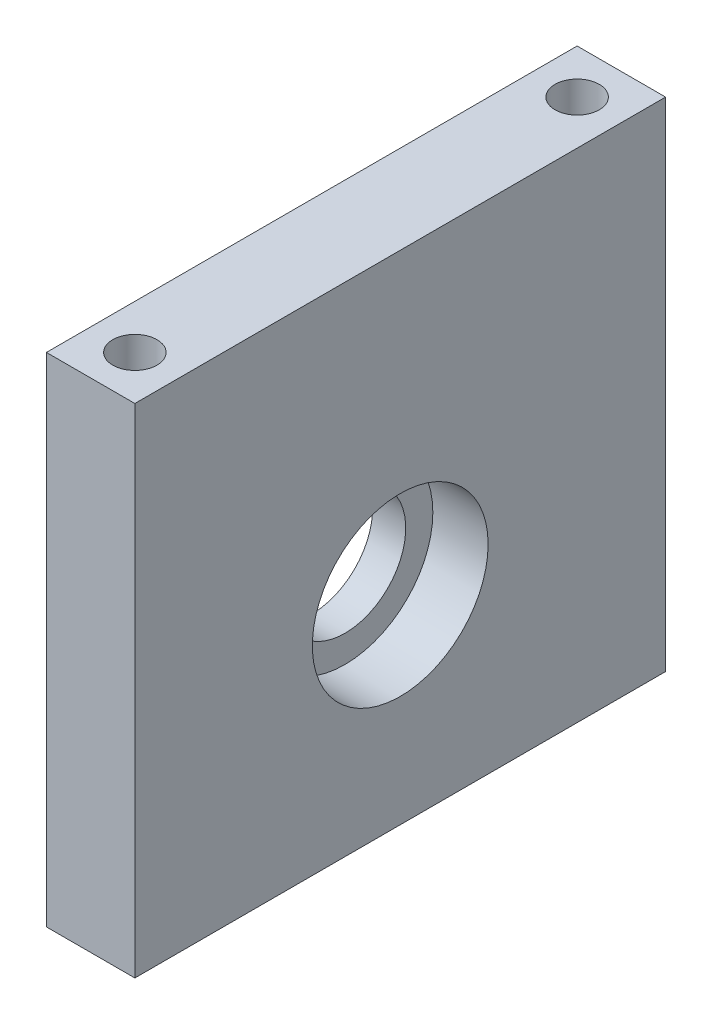
SolidWorks part; units mm, degrees
ref_plane "Plan de face" through (0, 0, 0) normal (0, 0, 1) x (1, 0, 0)
ref_plane "Plan de dessus" through (0, 0, 0) normal (0, 1, 0) x (1, 0, 0)
ref_plane "Plan de droite" through (0, 0, 0) normal (1, 0, 0) x (0, 0, -1)
sketch "Esquisse1" plane through (0, 0, 0) normal (0, 1, 0) x (1, 0, 0)
  line L17 (0, 0) -> (8, 0)
  line L19 (8, 0) -> (8, 48)
  line L20 (8, 48) -> (0, 48)
  line L21 (0, 48) -> (0, 0)
extrude "Boss.-Extru.1" add sketch "Esquisse1" along normal blind 45 contours L20 L21 L17 L19 region at (4, 0, -24)
sketch "Esquisse28" plane through (8, 0, 0) normal (1, 0, 0) x (0, 0, -1)
  line L0 (0, 0) -> (24, 0) construction
  line L1 (0, 0) -> (48, 0) construction
  line L2 (24, 0) -> (24, 18) construction
  circle A0 centre (24, 18) radius 7.95
  dimension "D1" = 15.9
  dimension "D2" = 18
  dimension "D3" = 24
extrude "Enlèv. mat.-Extru.1" cut sketch "Esquisse28" against normal blind 10
sketch "Esquisse29" plane through (0, 0, 0) normal (-1, 0, 0) x (0, 0, 1)
  circle A0 centre (-24, 18) radius 8.1
  circle A1 centre (-24, 18) radius 5.5
extrude "Boss.-Extru.2" add sketch "Esquisse29" against normal blind 3
sketch "Esquisse30" plane through (0, 0, 0) normal (0, -1, 0) x (1, 0, 0)
  line L0 (0, 0) -> (8, 0) construction
  line L1 (8, 0) -> (8, -8) construction
  line L2 (8, 0) -> (8, -48) construction
  line L3 (8, -8) -> (0, -8) construction
  line L4 (0, -48) -> (0, 0) construction
  line L5 (0, -8) -> (0, 0) construction
  line L6 (0, 0) -> (8, -8) construction
  line L7 (8, -8) -> (8, 0) construction
  line L8 (8, 0) -> (0, -8) construction
  line L9 (0, -48) -> (8, -48) construction
  line L10 (8, -48) -> (8, -40) construction
  line L11 (8, -40) -> (0, -40) construction
  line L12 (0, -48) -> (0, -40) construction
  line L13 (0, -40) -> (8, -48) construction
  line L14 (8, -48) -> (8, -40) construction
  line L15 (8, -40) -> (0, -48) construction
  circle A0 centre (4, -44) radius 2
  circle A1 centre (4, -4) radius 2
extrude "Enlèv. mat.-Extru.2" cut sketch "Esquisse30" against normal blind 15
sketch "Esquisse31" plane through (0, 45, 0) normal (0, 1, 0) x (1, 0, 0)
  line L0 (0, 0) -> (8, 0) construction
  line L1 (8, 0) -> (8, 48) construction
  line L2 (0, 0) -> (8, 0) construction
  line L3 (8, 0) -> (8, 8) construction
  line L4 (8, 8) -> (0, 8) construction
  line L5 (0, 48) -> (0, 0) construction
  line L6 (0, 8) -> (0, 0) construction
  line L7 (0, 0) -> (8, 8) construction
  line L8 (8, 8) -> (8, 0) construction
  line L9 (8, 0) -> (0, 8) construction
  line L10 (0, 48) -> (8, 48) construction
  line L11 (8, 48) -> (8, 40) construction
  line L12 (8, 40) -> (0, 40) construction
  line L13 (0, 40) -> (0, 48) construction
  line L14 (0, 48) -> (8, 40) construction
  line L15 (8, 40) -> (8, 48) construction
  line L16 (8, 48) -> (0, 40) construction
  circle A0 centre (4, 44) radius 2
  circle A1 centre (4, 4) radius 2
extrude "Enlèv. mat.-Extru.3" cut sketch "Esquisse31" against normal blind 15
